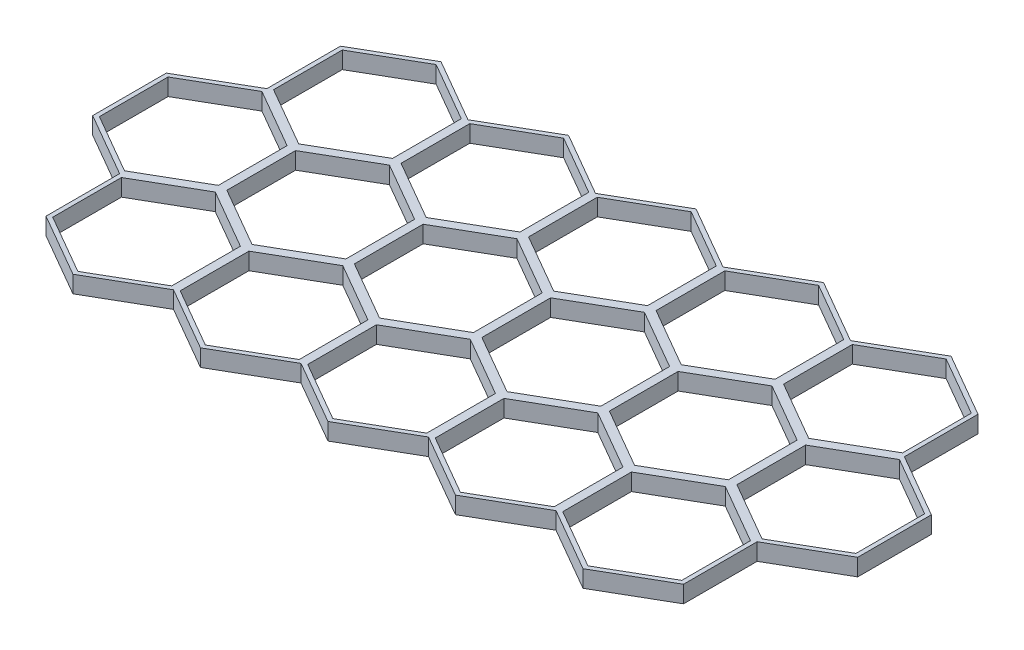
SolidWorks part; units mm, degrees
ref_plane "Front Plane" through (0, 0, 0) normal (0, 0, 1) x (1, 0, 0)
ref_plane "Top Plane" through (0, 0, 0) normal (0, 1, 0) x (1, 0, 0)
ref_plane "Right Plane" through (0, 0, 0) normal (1, 0, 0) x (0, 0, -1)
sketch "Sketch1" plane through (0, 0, 0) normal (0, 1, 0) x (1, 0, 0)
  line L0 (15, 8.0829) -> (8, 4.0415)
  line L1 (0, 8.6603) -> (-7.5, 4.3301)
  line L2 (-7.5, 4.3301) -> (-7.5, -4.3301)
  line L3 (-7.5, -4.3301) -> (0, -8.6603)
  line L4 (0, -8.6603) -> (7.5, -4.3301)
  line L5 (7.5, -4.3301) -> (7.5, 4.3301)
  line L6 (7.5, 4.3301) -> (0, 8.6603)
  line L7 (0, 8.0829) -> (-7, 4.0415)
  line L8 (-7, 4.0415) -> (-7, -4.0415)
  line L9 (-7, -4.0415) -> (0, -8.0829)
  line L10 (0, -8.0829) -> (7, -4.0415)
  line L11 (7, -4.0415) -> (7, 4.0415)
  line L12 (7, 4.0415) -> (0, 8.0829)
  line L13 (8, 4.0415) -> (8, -4.0415)
  line L14 (8, -4.0415) -> (15, -8.0829)
  line L15 (15, -8.0829) -> (22, -4.0415)
  line L16 (22, -4.0415) -> (22, 4.0415)
  line L17 (22, 4.0415) -> (15, 8.0829)
  line L18 (22.5, 4.3301) -> (15, 8.6603)
  line L19 (15, 8.6603) -> (7.5, 4.3301)
  line L20 (7.5, 4.3301) -> (7.5, -4.3301)
  line L21 (7.5, -4.3301) -> (15, -8.6603)
  line L22 (15, -8.6603) -> (22.5, -4.3301)
  line L23 (22.5, -4.3301) -> (22.5, 4.3301)
  line L24 (30, 8.0829) -> (23, 4.0415)
  line L25 (23, 4.0415) -> (23, -4.0415)
  line L26 (23, -4.0415) -> (30, -8.0829)
  line L27 (30, -8.0829) -> (37, -4.0415)
  line L28 (37, -4.0415) -> (37, 4.0415)
  line L29 (37, 4.0415) -> (30, 8.0829)
  line L30 (37.5, 4.3301) -> (30, 8.6603)
  line L31 (30, 8.6603) -> (22.5, 4.3301)
  line L32 (22.5, 4.3301) -> (22.5, -4.3301)
  line L33 (22.5, -4.3301) -> (30, -8.6603)
  line L34 (30, -8.6603) -> (37.5, -4.3301)
  line L35 (37.5, -4.3301) -> (37.5, 4.3301)
  line L36 (45, 8.0829) -> (38, 4.0415)
  line L37 (38, 4.0415) -> (38, -4.0415)
  line L38 (38, -4.0415) -> (45, -8.0829)
  line L39 (45, -8.0829) -> (52, -4.0415)
  line L40 (52, -4.0415) -> (52, 4.0415)
  line L41 (52, 4.0415) -> (45, 8.0829)
  line L42 (52.5, 4.3301) -> (45, 8.6603)
  line L43 (45, 8.6603) -> (37.5, 4.3301)
  line L44 (37.5, 4.3301) -> (37.5, -4.3301)
  line L45 (37.5, -4.3301) -> (45, -8.6603)
  line L46 (45, -8.6603) -> (52.5, -4.3301)
  line L47 (52.5, -4.3301) -> (52.5, 4.3301)
  line L48 (60, 8.0829) -> (53, 4.0415)
  line L49 (53, 4.0415) -> (53, -4.0415)
  line L50 (53, -4.0415) -> (60, -8.0829)
  line L51 (60, -8.0829) -> (67, -4.0415)
  line L52 (67, -4.0415) -> (67, 4.0415)
  line L53 (67, 4.0415) -> (60, 8.0829)
  line L54 (67.5, 4.3301) -> (60, 8.6603)
  line L55 (60, 8.6603) -> (52.5, 4.3301)
  line L56 (52.5, 4.3301) -> (52.5, -4.3301)
  line L57 (52.5, -4.3301) -> (60, -8.6603)
  line L58 (60, -8.6603) -> (67.5, -4.3301)
  line L59 (67.5, -4.3301) -> (67.5, 4.3301)
  line L60 (7.5, -4.9075) -> (0.5, -8.9489)
  line L61 (-7.5, -4.3301) -> (-15, -8.6603)
  line L62 (-15, -8.6603) -> (-15, -17.3205)
  line L63 (-15, -17.3205) -> (-7.5, -21.6506)
  line L64 (-7.5, -21.6506) -> (0, -17.3205)
  line L65 (0, -17.3205) -> (0, -8.6603)
  line L66 (0, -8.6603) -> (-7.5, -4.3301)
  line L67 (-7.5, -4.9075) -> (-14.5, -8.9489)
  line L68 (-14.5, -8.9489) -> (-14.5, -17.0318)
  line L69 (-14.5, -17.0318) -> (-7.5, -21.0733)
  line L70 (-7.5, -21.0733) -> (-0.5, -17.0318)
  line L71 (-0.5, -17.0318) -> (-0.5, -8.9489)
  line L72 (-0.5, -8.9489) -> (-7.5, -4.9075)
  line L73 (0.5, -8.9489) -> (0.5, -17.0318)
  line L74 (0.5, -17.0318) -> (7.5, -21.0733)
  line L75 (7.5, -21.0733) -> (14.5, -17.0318)
  line L76 (14.5, -17.0318) -> (14.5, -8.9489)
  line L77 (14.5, -8.9489) -> (7.5, -4.9075)
  line L78 (7.5, -4.3301) -> (0, -8.6603)
  line L79 (0, -8.6603) -> (0, -17.3205)
  line L80 (0, -17.3205) -> (7.5, -21.6506)
  line L81 (7.5, -21.6506) -> (15, -17.3205)
  line L82 (7.5, -4.3301) -> (15, -8.6603)
  line L83 (15, -17.3205) -> (15, -8.6603)
  line L84 (22.5, -4.9075) -> (15.5, -8.9489)
  line L85 (15.5, -8.9489) -> (15.5, -17.0318)
  line L86 (15.5, -17.0318) -> (22.5, -21.0733)
  line L87 (22.5, -21.0733) -> (29.5, -17.0318)
  line L88 (29.5, -17.0318) -> (29.5, -8.9489)
  line L89 (29.5, -8.9489) -> (22.5, -4.9075)
  line L90 (22.5, -4.3301) -> (15, -8.6603)
  line L91 (15, -8.6603) -> (15, -17.3205)
  line L92 (15, -17.3205) -> (22.5, -21.6506)
  line L93 (22.5, -21.6506) -> (30, -17.3205)
  line L94 (22.5, -4.3301) -> (30, -8.6603)
  line L95 (30, -17.3205) -> (30, -8.6603)
  line L96 (37.5, -4.9075) -> (30.5, -8.9489)
  line L97 (30.5, -8.9489) -> (30.5, -17.0318)
  line L98 (30.5, -17.0318) -> (37.5, -21.0733)
  line L99 (37.5, -21.0733) -> (44.5, -17.0318)
  line L100 (44.5, -17.0318) -> (44.5, -8.9489)
  line L101 (44.5, -8.9489) -> (37.5, -4.9075)
  line L102 (37.5, -4.3301) -> (30, -8.6603)
  line L103 (30, -8.6603) -> (30, -17.3205)
  line L104 (30, -17.3205) -> (37.5, -21.6506)
  line L105 (37.5, -21.6506) -> (45, -17.3205)
  line L106 (37.5, -4.3301) -> (45, -8.6603)
  line L107 (45, -17.3205) -> (45, -8.6603)
  line L108 (52.5, -4.9075) -> (45.5, -8.9489)
  line L109 (45.5, -8.9489) -> (45.5, -17.0318)
  line L110 (45.5, -17.0318) -> (52.5, -21.0733)
  line L111 (52.5, -21.0733) -> (59.5, -17.0318)
  line L112 (59.5, -17.0318) -> (59.5, -8.9489)
  line L113 (59.5, -8.9489) -> (52.5, -4.9075)
  line L114 (52.5, -4.3301) -> (45, -8.6603)
  line L115 (45, -8.6603) -> (45, -17.3205)
  line L116 (45, -17.3205) -> (52.5, -21.6506)
  line L117 (52.5, -21.6506) -> (60, -17.3205)
  line L118 (52.5, -4.3301) -> (60, -8.6603)
  line L119 (60, -17.3205) -> (60, -8.6603)
  line L120 (67.5, -4.9075) -> (60.5, -8.9489)
  line L121 (60.5, -8.9489) -> (60.5, -17.0318)
  line L122 (60.5, -17.0318) -> (67.5, -21.0733)
  line L123 (67.5, -21.0733) -> (74.5, -17.0318)
  line L124 (74.5, -17.0318) -> (74.5, -8.9489)
  line L125 (74.5, -8.9489) -> (67.5, -4.9075)
  line L126 (67.5, -4.3301) -> (60, -8.6603)
  line L127 (60, -8.6603) -> (60, -17.3205)
  line L128 (60, -17.3205) -> (67.5, -21.6506)
  line L129 (67.5, -21.6506) -> (75, -17.3205)
  line L130 (67.5, -4.3301) -> (75, -8.6603)
  line L131 (75, -17.3205) -> (75, -8.6603)
  line L133 (60, -17.3205) -> (67.5, -21.6506)
  line L134 (67.5, -21.6506) -> (67.5, -30.3109)
  line L135 (60, -34.641) -> (52.5, -30.3109)
  line L136 (67.5, -30.3109) -> (60, -34.641)
  line L137 (52.5, -21.6506) -> (60, -17.3205)
  line L138 (52.5, -21.6506) -> (52.5, -30.3109)
  line L139 (45, -17.3205) -> (52.5, -21.6506)
  line L140 (37.5, -21.6506) -> (45, -17.3205)
  line L141 (37.5, -30.3109) -> (37.5, -21.6506)
  line L142 (45, -34.641) -> (37.5, -30.3109)
  line L143 (52.5, -30.3109) -> (45, -34.641)
  line L144 (37.5, -21.6506) -> (37.5, -30.3109)
  line L145 (30, -17.3205) -> (37.5, -21.6506)
  line L146 (22.5, -21.6506) -> (30, -17.3205)
  line L147 (22.5, -30.3109) -> (22.5, -21.6506)
  line L148 (30, -34.641) -> (22.5, -30.3109)
  line L149 (37.5, -30.3109) -> (30, -34.641)
  line L150 (22.5, -21.6506) -> (22.5, -30.3109)
  line L151 (15, -17.3205) -> (22.5, -21.6506)
  line L152 (7.5, -21.6506) -> (15, -17.3205)
  line L153 (7.5, -30.3109) -> (7.5, -21.6506)
  line L154 (15, -34.641) -> (7.5, -30.3109)
  line L155 (22.5, -30.3109) -> (15, -34.641)
  line L156 (7.5, -21.6506) -> (7.5, -30.3109)
  line L157 (0, -17.3205) -> (7.5, -21.6506)
  line L158 (-7.5, -21.6506) -> (0, -17.3205)
  line L159 (-7.5, -30.3109) -> (-7.5, -21.6506)
  line L160 (0, -34.641) -> (-7.5, -30.3109)
  line L161 (7.5, -30.3109) -> (0, -34.641)
  line L162 (67, -30.0222) -> (60, -34.0637)
  line L163 (67, -21.9393) -> (67, -30.0222)
  line L164 (60, -17.8979) -> (67, -21.9393)
  line L165 (53, -21.9393) -> (60, -17.8979)
  line L166 (53, -30.0222) -> (53, -21.9393)
  line L167 (60, -34.0637) -> (53, -30.0222)
  line L168 (52, -30.0222) -> (45, -34.0637)
  line L169 (52, -21.9393) -> (52, -30.0222)
  line L170 (45, -17.8979) -> (52, -21.9393)
  line L171 (38, -21.9393) -> (45, -17.8979)
  line L172 (38, -30.0222) -> (38, -21.9393)
  line L173 (45, -34.0637) -> (38, -30.0222)
  line L174 (37, -30.0222) -> (30, -34.0637)
  line L175 (37, -21.9393) -> (37, -30.0222)
  line L176 (30, -17.8979) -> (37, -21.9393)
  line L177 (23, -21.9393) -> (30, -17.8979)
  line L178 (23, -30.0222) -> (23, -21.9393)
  line L179 (30, -34.0637) -> (23, -30.0222)
  line L180 (22, -30.0222) -> (15, -34.0637)
  line L181 (22, -21.9393) -> (22, -30.0222)
  line L182 (15, -17.8979) -> (22, -21.9393)
  line L183 (8, -21.9393) -> (15, -17.8979)
  line L184 (8, -30.0222) -> (8, -21.9393)
  line L185 (15, -34.0637) -> (8, -30.0222)
  line L186 (7, -30.0222) -> (0, -34.0637)
  line L187 (7, -21.9393) -> (7, -30.0222)
  line L188 (0, -17.8979) -> (7, -21.9393)
  line L189 (-7, -21.9393) -> (0, -17.8979)
  line L190 (-7, -30.0222) -> (-7, -21.9393)
  line L191 (0, -34.0637) -> (-7, -30.0222)
  circle A0 centre (0, 0) radius 7.5 construction
  circle A1 centre (0, 0) radius 7 construction
  circle A2 centre (-7.5, -12.9904) radius 7.5 construction
  circle A3 centre (-7.5, -12.9904) radius 7 construction
  dimension "D1" = 15
  dimension "D2" = 14
  dimension "D4" = 15
  dimension "D5" = 14
  dimension "D3" = 5
  dimension "D6" = 6
extrude "Boss-Extrude1" add sketch "Sketch1" along normal blind 2 contours L5 L6 L1 L2 L3 L4 L12 L11 L10 L9 L8 L7 | L22 L23 L18 L19 L5 L21 L17 L16 L15 L14 L13 L0 | L34 L35 L30 L31 L23 L33 L29 L28 L27 L26 L25 L24 | L46 L47 L42 L43 L35 L45 L41 L40 L39 L38 L37 L36 | L58 L59 L54 L55 L47 L57 L53 L52 L51 L50 L49 L48 | L64 L65 L3 L61 L62 L63 L72 L71 L70 L69 L68 L67 | L81 L83 L21 L4 L65 L80 L77 L76 L75 L74 L73 L60 | L93 L95 L33 L22 L83 L92 L89 L88 L87 L86 L85 L84 | L149 L141 L104 L93 L147 L148 L174 L179 L178 L177 L176 L175 | L155 L147 L92 L81 L153 L154 L180 L185 L184 L183 L182 L181 | L161 L153 L80 L64 L159 L160 L186 L191 L190 L189 L188 L187 | L117 L138 L135 L136 L134 L128 L162 L167 L166 L165 L164 L163 | L143 L138 L116 L105 L141 L142 L168 L173 L172 L171 L170 L169 | L105 L107 L45 L34 L95 L104 L101 L100 L99 L98 L97 L96 | L117 L119 L57 L46 L107 L116 L113 L112 L111 L110 L109 L108 | L129 L131 L130 L58 L119 L128 L125 L124 L123 L122 L121 L120 region at (3.6354, 0, -6.2968) region at (11.3646, 0, -6.2968) region at (-3.8646, 0, 6.6936) region at (11.1354, 0, 6.6936) region at (18.8646, 0, 6.6936) region at (26.3646, 0, -6.2968) region at (3.6354, 0, 19.684) region at (18.6354, 0, 19.684) region at (33.8646, 0, 6.6936) region at (26.3646, 0, 19.684) region at (41.3646, 0, -6.2968) region at (48.8646, 0, 6.6936) region at (41.3646, 0, 19.684) region at (56.3646, 0, -6.2968) region at (63.8646, 0, 6.6936) region at (56.3646, 0, 19.684)
